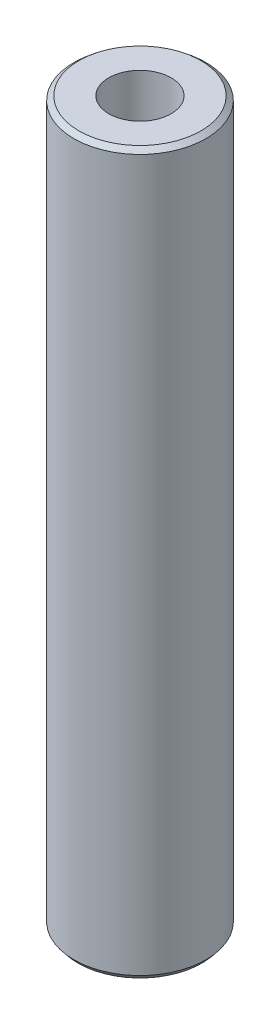
SolidWorks part; units mm, degrees
ref_plane "Front Plane" through (0, 0, 0) normal (0, 0, 1) x (1, 0, 0)
ref_plane "Top Plane" through (0, 0, 0) normal (0, 1, 0) x (1, 0, 0)
ref_plane "Right Plane" through (0, 0, 0) normal (1, 0, 0) x (0, 0, -1)
sketch "Sketch1" plane through (0, 0, 0) normal (0, 1, 0) x (1, 0, 0)
  circle A0 centre (0, 0) radius 55
  dimension "SHAFT_OD" = 110
extrude "Boss-Extrude1" add sketch "Sketch1" along normal blind 600
sketch "Sketch2" plane through (0, 0, 0) normal (0, 1, 0) x (1, 0, 0)
  circle A0 centre (0, 0) radius 25.9896
  dimension "BORE_D" = 51.9792
extrude "Cut-Extrude1" cut sketch "Sketch2" along normal through all
chamfer "Chamfer1" distance 3.4595 angle 50.685 2 edges at (0, 600, 55) (0, 0, 55) first distance on face at (0, 600, 55) first distance on face at (0, 0, 25.9896)
